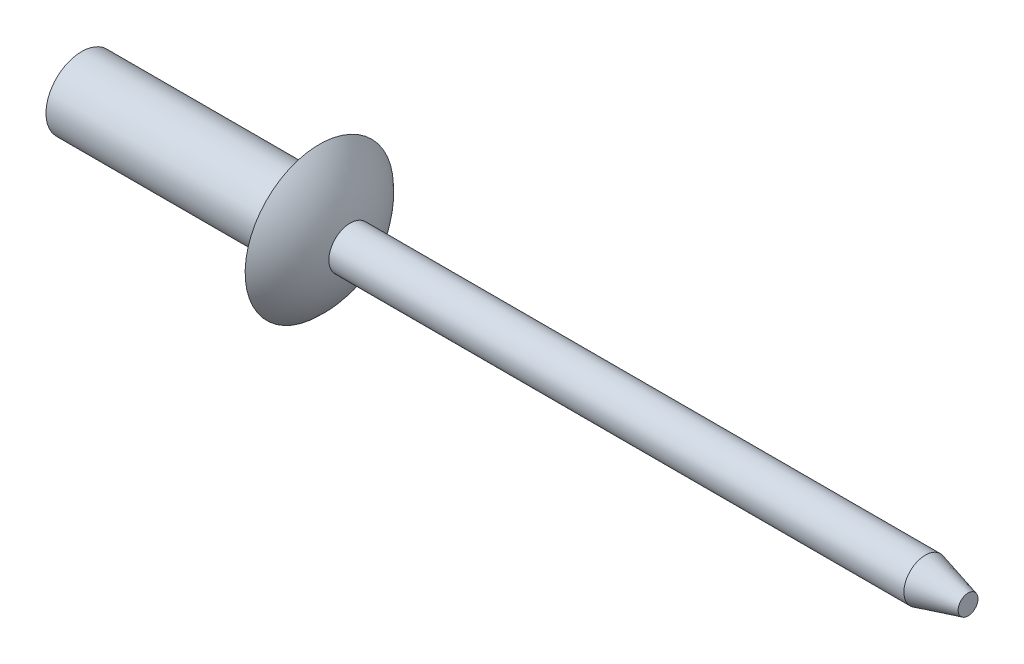
SolidWorks part; units mm, degrees
ref_plane "Front" through (0, 0, 0) normal (0, 0, 1) x (1, 0, 0)
ref_plane "Top" through (0, 0, 0) normal (0, 1, 0) x (1, 0, 0)
ref_plane "Right" through (0, 0, 0) normal (1, 0, 0) x (0, 0, -1)
sketch "Sketch1" plane through (-11.6035, 14.7235, 0) normal (0, 0, 1) x (0, -1, 0)
  line L0 (14.7235, 11.6035) -> (16.2235, 11.6035)
  line L1 (16.2235, 11.6035) -> (16.2235, 21.6035)
  line L2 (16.2235, 21.6035) -> (17.8435, 21.6035)
  line L3 (14.7235, 34.3377) -> (14.7235, -10.975) construction
  line L4 (15.6235, 22.9053) -> (15.6235, 48.9053)
  line L5 (15.6235, 48.9053) -> (14.7235, 48.9053)
  line L6 (14.7235, 11.6035) -> (14.7235, 48.9053)
  arc A0 (17.8435, 21.6035) -> (15.6235, 22.9053) centre (14.7235, 18.8269) ccw
revolve "Base-Revolve" add sketch "Sketch1" angle 360 about L3
fillet "Fillet1" radius 0.5 1 edges at (10, 1.5, 0)
chamfer "Chamfer1" distance 1.8 angle 15 1 edges at (37.3019, 0.9, 0) first distance on face at (37.3019, 0.9, 0)
equation "\"D1@Chamfer1\" = \"d1@Sketch1\""
